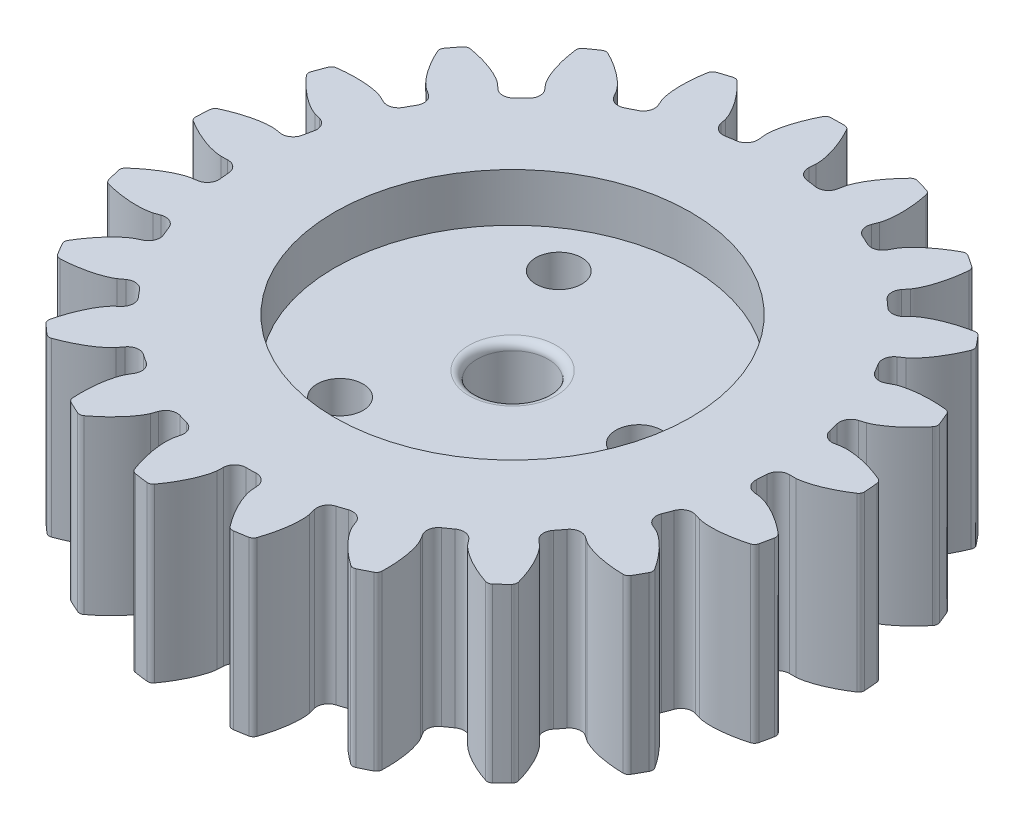
SolidWorks part; units mm, degrees
material "Acero aleado"
ref_plane "Alzado" through (0, 0, 0) normal (0, 0, 1) x (1, 0, 0)
ref_plane "Planta" through (0, 0, 0) normal (0, 1, 0) x (1, 0, 0)
ref_plane "Vista lateral" through (0, 0, 0) normal (1, 0, 0) x (0, 0, -1)
sketch "Croquis1" plane through (0, 0, 0) normal (0, 1, 0) x (1, 0, 0)
  line L0 (0, 0) -> (24.6669, 0)
  line L1 (0, 0) -> (26.2471, 0.3912) construction
  line L2 (0, 0) -> (28.6344, 2.5757)
  line L4 (0, 0) -> (28.6985, -1.7208)
  circle A0 centre (0, 0) radius 26.25 construction
  circle A1 centre (0, 0) radius 28.75
  circle A2 centre (0, 0) radius 24.6669
  circle A3 centre (0, 0) radius 28.75 construction
  circle A4 centre (0, 0) radius 23.125
  arc A6 (28.6985, -1.7208) -> (28.6996, 1.7022) centre (0, 0) ccw
  spline S0 degree 4 poles (24.6669, 0) (24.6735, 0.0001) (24.6918, 0.0006) (24.7264, 0.0025) (24.7829, 0.0071) (24.8548, 0.0151) (24.9476, 0.0278) (25.0567, 0.0459) (25.1763, 0.0691) (25.3062, 0.0978) (25.4354, 0.1295) (25.564, 0.1641) (25.6918, 0.2011) (25.8461, 0.249) (26.0306, 0.3107) (26.2453, 0.3889) (26.4876, 0.485) (26.7331, 0.5906) (26.9735, 0.7009) (27.2148, 0.8196) (27.4473, 0.9397) (27.6871, 1.0717) (27.9076, 1.1974) (28.1526, 1.3463) (28.3497, 1.4688) (28.6075, 1.6391) (28.7591, 1.7422) (28.9356, 1.8659) (29.0136, 1.9223) (29.0616, 1.957) knots 0 0 0 0 0 0.005377 0.015084 0.028532 0.04661 0.064855 0.092111 0.119476 0.146842 0.174209 0.201575 0.228941 0.256307 0.307035 0.361767 0.4165 0.471232 0.525964 0.580697 0.635429 0.690161 0.744894 0.799626 0.854358 0.909091 0.954545 1 1 1 1 1 construction
  spline S1 degree 4 poles (24.6669, 0) (24.6735, 0.0001) (24.6918, 0.0006) (24.7264, 0.0025) (24.7829, 0.0071) (24.8548, 0.0151) (24.9476, 0.0278) (25.0567, 0.0459) (25.1763, 0.0691) (25.3062, 0.0978) (25.4354, 0.1295) (25.564, 0.1641) (25.6918, 0.2011) (25.8461, 0.249) (26.0306, 0.3107) (26.2453, 0.3889) (26.4876, 0.485) (26.7331, 0.5906) (26.9735, 0.7009) (27.2148, 0.8196) (27.4473, 0.9397) (27.6871, 1.0717) (27.9076, 1.1974) (28.1526, 1.3463) (28.3497, 1.4688) (28.5516, 1.6022) (28.6496, 1.6681) (28.6996, 1.7022) knots 0 0 0 0 0 0.005377 0.015084 0.028532 0.04661 0.064855 0.092111 0.119476 0.146842 0.174209 0.201575 0.228941 0.256307 0.307035 0.361767 0.4165 0.471232 0.525964 0.580697 0.635429 0.690161 0.744894 0.799626 0.854358 0.909091 0.909091 0.909091 0.909091 0.909091
  dimension "D1" = 52.5
  dimension "D2" = 57.5
  dimension "D3" = 49.3339
  dimension "D4" = 46.25
  dimension "D5" = 8.571
  dimension "D6" = 4.286
extrude "Saliente-Extruir4" add sketch "Croquis1" along normal blind 15 contours L0 A4 L2 | L4 A4 L0 | A4 L0 A2 L2 | A2 S1 A1 L2 region at (15.396, 0, -0.6911) region at (15.4075, 0, 0.4615) region at (23.8722, 0, -1.0715) region at (26.3912, 0, -1.4582)
sketch "Croquis10" plane through (0, 15, 0) normal (0, 1, 0) x (1, 0, 0)
  line L0 (0, 0) -> (23.0835, -1.3841)
  line L1 (0, 0) -> (23.0835, -1.3841)
  line L2 (0, 0) -> (28.6344, 2.5757)
  line L3 (0, 0) -> (28.6344, 2.5757)
  line L4 (-10.15, 1.65) -> (10.15, 1.65)
  line L5 (-10, -1.5) -> (10, -1.5) construction
  line L6 (-10, -1.5) -> (-10, 1.5) construction
  line L7 (-10, 1.5) -> (10, 1.5) construction
  line L8 (10, -1.5) -> (10, 1.5) construction
  line L9 (-10, -1.5) -> (10, 1.5) construction
  line L10 (-10, 1.5) -> (10, -1.5) construction
  line L11 (10.15, -1.65) -> (10.15, 1.65)
  line L12 (-10.15, -1.65) -> (10.15, -1.65)
  line L13 (-10.15, -1.65) -> (-10.15, 1.65)
  circle A0 centre (0, 0) radius 23.125
  arc A2 (28.6996, 1.7022) -> (28.6344, 2.5757) centre (0, 0) ccw
  circle A7 centre (0, 0) radius 3 construction
  circle A8 centre (0, 0) radius 3.15
  arc A9 (28.6996, 1.7022) -> (28.6344, 2.5757) centre (0, 0) ccw
  spline S0 degree 4 poles (4.6481, 999.7911) (22.7503, 13.8395) (23.4033, 0.223) (24.0945, -0.0489) (24.7829, 0.0071) (24.8548, 0.0151) (24.9476, 0.0278) (25.0567, 0.0459) (25.1763, 0.0691) (25.3062, 0.0978) (25.4354, 0.1295) (25.564, 0.1641) (25.6918, 0.2011) (25.8461, 0.249) (26.0306, 0.3107) (26.2453, 0.3889) (26.4876, 0.485) (26.7331, 0.5906) (26.9735, 0.7009) (27.2148, 0.8196) (27.4473, 0.9397) (27.6871, 1.0717) (27.9076, 1.1974) (28.1526, 1.3463) (29.0466, 1.902) (31.6551, 3.7794) (3.8223, -15.0185) (854.5089, 565.6312) knots -0.521457 -0.521457 -0.521457 -0.521457 -0.521457 0.005377 0.015084 0.028532 0.04661 0.064855 0.092111 0.119476 0.146842 0.174209 0.201575 0.228941 0.256307 0.307035 0.361767 0.4165 0.471232 0.525964 0.580697 0.635429 0.690161 0.744894 0.799626 0.854358 1.68299 1.68299 1.68299 1.68299 1.68299 only from (24.6669, 0) to (28.6996, 1.7022)
  spline S1 degree 4 poles (24.6669, 0) (24.6735, 0.0001) (24.6918, 0.0006) (24.7264, 0.0025) (24.7829, 0.0071) (24.8548, 0.0151) (24.9476, 0.0278) (25.0567, 0.0459) (25.1763, 0.0691) (25.3062, 0.0978) (25.4354, 0.1295) (25.564, 0.1641) (25.6918, 0.2011) (25.8461, 0.249) (26.0306, 0.3107) (26.2453, 0.3889) (26.4876, 0.485) (26.7331, 0.5906) (26.9735, 0.7009) (27.2148, 0.8196) (27.4473, 0.9397) (27.6871, 1.0717) (27.9076, 1.1974) (28.1526, 1.3463) (28.3497, 1.4688) (28.5516, 1.6022) (28.6496, 1.6681) (28.6996, 1.7022) knots 0 0 0 0 0 0.005377 0.015084 0.028532 0.04661 0.064855 0.092111 0.119476 0.146842 0.174209 0.201575 0.228941 0.256307 0.307035 0.361767 0.4165 0.471232 0.525964 0.580697 0.635429 0.690161 0.744894 0.799626 0.854358 0.909091 0.909091 0.909091 0.909091 0.909091
  spline S3 degree 3 poles (17.6092, 0.01) (17.7752, 0.0086) (18.1032, 0.0814) (18.7425, 0.2684) (19.5069, 0.611) (20.3688, 1.1202) (20.9089, 1.5158) (21.1699, 1.7241) knots -0.002288 -0.002288 -0.002288 -0.002288 0.111468 0.225224 0.452736 0.680248 0.907761 0.907761 0.907761 0.907761
  line M6 (28.6344, 2.5757) -> (0, 0)
  line M7 (0, 0) -> (23.0835, -1.3841)
  dimension "D3" = 3
  dimension "D4" = 20
  dimension "D5" = 0.15
  dimension "D6" = 0.15
fillet "Redondeo5" radius 1 1 edges at (23.125, 7.5, 0)
fillet "Redondeo6" radius 0.5 1 edges at (28.6996, 7.5, -1.7022)
mirror "Simetría1" about plane through (0, 15, 0) normal (-0.0896, 0, -0.996) of "Redondeo6", "Saliente-Extruir4", "Redondeo5"
pattern_circular "MatrizC8" count 21 over 360 about axis through (0, 15, 0) along (0, -1, 0) reverse direction yes of bodies 160
extrude "Saliente-Extruir6" add sketch "Croquis10" against normal up to surface (15 mm away) contours M6 M7 | M6 M7 region at (2.0978, 15, -0.0313) region at (-0.0817, 15, 0.0012) up to face at (22.9112, 0, -2.0609)
sketch "Croquis11" plane through (0, 0, 0) normal (0, -1, 0) x (1, 0, 0)
  circle A0 centre (0, 0) radius 3.1
  circle A2 centre (0, 0) radius 10
  dimension "D1" = 6.2
  dimension "D2" = 20
extrude "Cortar-Extruir5" cut sketch "Croquis11" against normal through all contours A0 region at (0, 0, 0)
sketch "Croquis12" plane through (0, 0, 0) normal (0, -1, 0) x (1, 0, 0)
  circle A0 centre (0, 0) radius 6.5
  circle A1 centre (0, 0) radius 3.1 construction
  circle A2 centre (0, 0) radius 3.1
  dimension "D1" = 13
extrude "Saliente-Extruir7" add sketch "Croquis12" along normal blind 2
sketch "Croquis13" plane through (0, 15, 0) normal (0, 1, 0) x (1, 0, 0)
  line L0 (0, 0) -> (11, 0)
  circle A0 centre (11, 0) radius 2
  circle A1 centre (-5.5, -9.5263) radius 2
  circle A2 centre (-5.5, 9.5263) radius 2
  dimension "D1" = 4
  dimension "D2" = 11
  dimension "D3" = 3
extrude "Cortar-Extruir6" cut sketch "Croquis13" against normal blind 12 contours A2 | A0 | A1 | A1 | A2 region at (11, 15, 1.9434) region at (-5.5, 15, 9.5263) region at (-5.5, 15, -9.5263)
sketch "Croquis14" plane through (0, 15, 0) normal (0, 1, 0) x (1, 0, 0)
  circle A0 centre (0, 0) radius 15.5
  dimension "D1" = 31
extrude "Cortar-Extruir7" cut sketch "Croquis14" against normal blind 4.2
fillet "Redondeo7" radius 0.7 1 edges at (0, 10.8, 3.1)
equation "\"D4@Croquis10\"=\"Cvarilla\""
equation "\"D3@Croquis10\"=\"Avarilla\""
equation "\"D2@Croquis10\"=\"Dvarilla\""
equation "\"D4@Croquis1\"= \"df\""
equation "\"d\"= \"Z\" * \"m\""
equation "\"Z\"= 21"
equation "\"m\"= 2.5mm"
equation "\"da\"= ( \"d\" + \"m\" * 2 ) * 1mm"
equation "\"df\"= \"d\" - \"m\" * 2.5"
equation "\"alpha\"= 20°"
equation "\"db\"= ( \"d\" * cos ( \"alpha\" ) ) * 1mm"
equation "\"p\"= \"m\" * pi"
equation "\"s\"= \"m\" * pi / 2"
equation "\"rb\"= \"db\" / 2"
equation "\"ra\"= \"da\" / 2"
equation "\"t_max\"= sqr ( ( \"ra\" / \"rb\" ) ^ 2 - 1 )"
equation "\"theta\"= ( \"m\" / \"d\" * pi ) * 1rad"
equation "\"D1@Croquis1\"=\"d\""
equation "\"D2@Croquis1\"=\"da\""
equation "\"D3@Croquis1\"=\"db\""
equation "\"D5@Croquis1\"=360/(\"Z\"*2)"
equation "\"D6@Croquis1\"= \"theta\" / 2"
equation "\"b\"= 15mm"
equation "\"redon\"= \"m\" * 0.1"
equation "\"D1@Saliente-Extruir4\"=\"b\""
equation "\"offset\"= 0.15"
equation "\"D1@MatrizC8\"=\"Z\""
equation "\"Dvarilla\"= 6mm"
equation "\"Avarilla\"= 3mm"
equation "\"Bvarilla\"= 10mm"
equation "\"Cvarilla\"= 20mm"
equation "\"D1@Croquis11\"=6.2"
